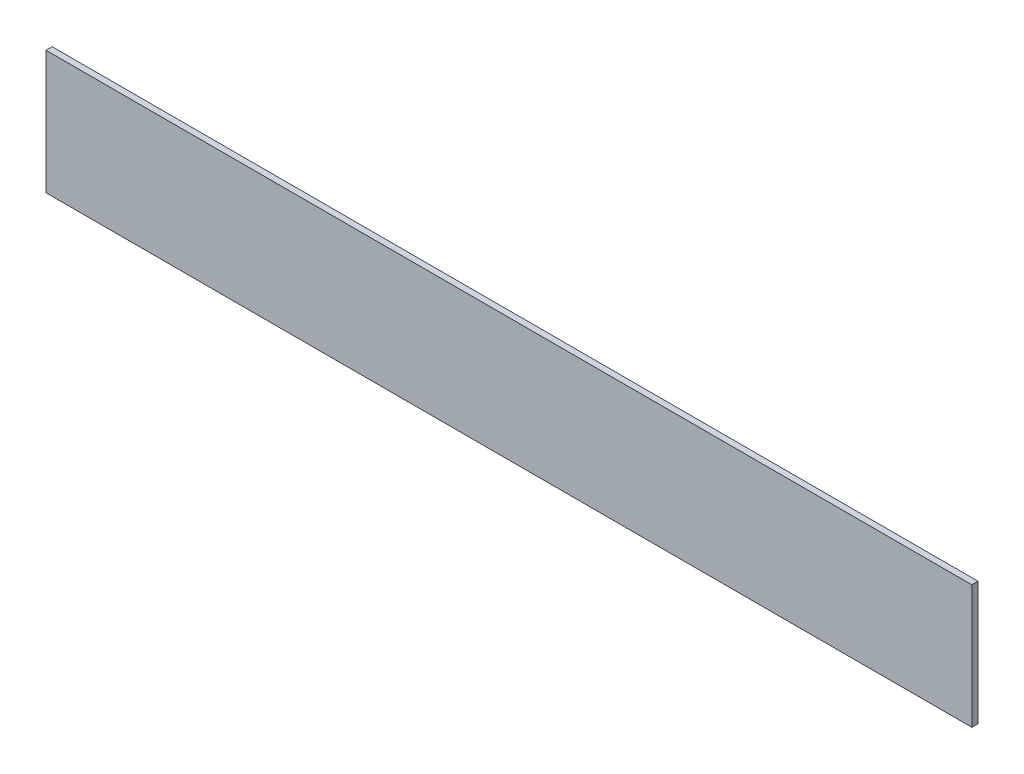
SolidWorks part; units mm, degrees
ref_plane "正面" through (0, 0, 0) normal (0, 0, 1) x (1, 0, 0)
ref_plane "平面"
ref_plane "右側面" through (0, 0, 0) normal (1, 0, 0) x (0, 0, -1)
sketch "ｽｹｯﾁ1" plane through (0, 0, 0) normal (0, 0, 1) x (1, 0, 0)
  line L1 (-150, -20) -> (150, -20)
  line L2 (-150, -20) -> (-150, 20)
  line L3 (-150, 20) -> (150, 20)
  line L4 (150, -20) -> (150, 20)
  line L5 (-150, -20) -> (150, 20) construction
  line L6 (-150, 20) -> (150, -20) construction
  point P0 (0, 0)
extrude "ﾎﾞｽ - 押し出し1" add sketch "ｽｹｯﾁ1" along normal blind 1 and the other way blind 1
sketch "ｽｹｯﾁ2" plane through (0, 0, 0) normal (0, 1, 0) x (1, 0, 0)
  line L0 (0, 0) -> (0, 500)
